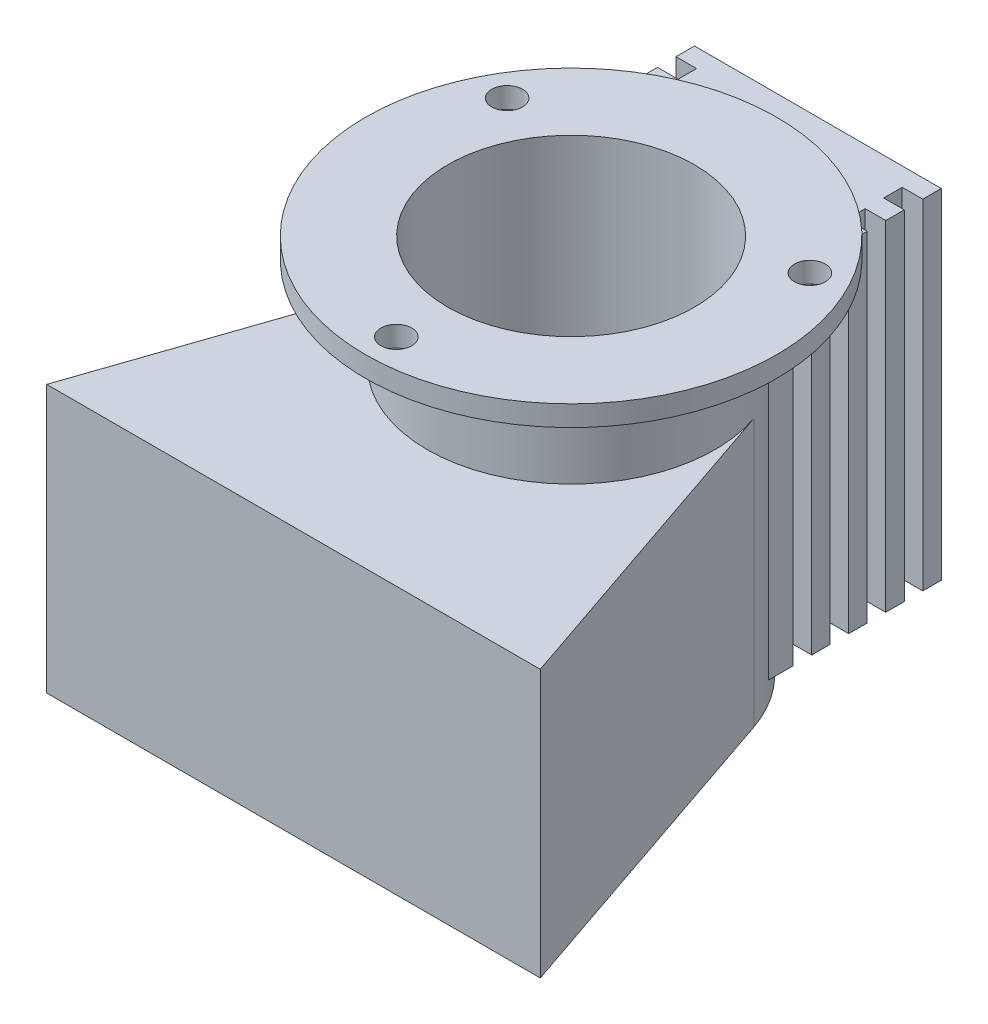
SolidWorks part; units mm, degrees
ref_plane "Front Plane" through (0, 0, 0) normal (0, 0, 1) x (1, 0, 0)
ref_plane "Top Plane" through (0, 0, 0) normal (0, 1, 0) x (1, 0, 0)
ref_plane "Right Plane" through (0, 0, 0) normal (1, 0, 0) x (0, 0, -1)
sketch "Sketch1" plane through (0, 0, 0) normal (0, 1, 0) x (1, 0, 0)
  line L0 (0, 11.2625) -> (0, -11.62) construction
  line L1 (-17.5363, 0) -> (17.5363, 0) construction
  line L2 (-6, -6.75) -> (6, -6.75)
  line L3 (-6, -6.75) -> (-3.3126, 1.1298)
  line L4 (6, -6.75) -> (3.3126, 1.1298)
  circle A0 centre (0, 0) radius 3.5
  point P9 (0, -6.75)
  dimension "D1" = 7
  dimension "D2" = 12
  dimension "D3" = 6.75
extrude "Boss-Extrude2" add sketch "Sketch1" along normal blind 8.75 contours A0 L3 region at (0, 0, 0)
extrude "Boss-Extrude3" add sketch "Sketch1<3>" along normal blind 6.5 contours A0 L3 L2 L4 region at (0, 0, 4.5241)
sketch "Sketch1<3>" plane through (0, 0, 0) normal (0, 1, 0) x (1, 0, 0) same geometry as "Sketch1"
sketch "Sketch2" plane through (0, 8.75, 0) normal (0, 1, 0) x (1, 0, 0)
  circle A0 centre (0, 0) radius 5
  dimension "D1" = 10
extrude "Boss-Extrude4" add sketch "Sketch2" along normal blind 0.5 contours A0
ref_plane "Plane1" through (0, 0, -6) normal (0, 0, 1) x (1, 0, 0)
sketch "Sketch4" plane through (0, 0, -6) normal (0, 0, 1) x (1, 0, 0)
  line L0 (-3.3126, 0) -> (3.3126, 0) construction
  line L1 (3, 0.5) -> (-3, 0.5)
  line L2 (3, 0.5) -> (3, 8.75)
  line L3 (3, 8.75) -> (-3, 8.75)
  line L4 (-3, 0.5) -> (-3, 8.75)
  point P4 (0, 0.5)
  dimension "D1" = 6
  dimension "D2" = 8.25
  dimension "D3" = 0.5
extrude "Boss-Extrude5" add sketch "Sketch4" along normal blind 6
sketch "Sketch5" plane through (0, 8.75, 0) normal (0, 1, 0) x (1, 0, 0)
  line L0 (3, 5.55) -> (3, 5.1)
  line L1 (3, 4) -> (3, 6) construction
  line L2 (3, 5.55) -> (2.5, 5.55)
  line L3 (2.5, 5.55) -> (2.5, 5.1)
  line L4 (2.5, 5.1) -> (3, 5.1)
  line L5 (3, 6) -> (-3, 6) construction
  dimension "D1" = 0.45
  dimension "D2" = 0.45
  dimension "D3" = 0.5
extrude "Cut-Extrude2" cut sketch "Sketch5" against normal through all
pattern_linear "LPattern1" count 4 spacing 0.9 along (0, 0, 1) count 2 spacing 5.5 along (-1, 0, 0) of "Cut-Extrude2"
sketch "Sketch6" plane through (0, 9.25, 0) normal (0, 1, 0) x (1, 0, 0)
  circle A0 centre (0, 0) radius 3
  circle A1 centre (0, 0) radius 0.75
  dimension "D1" = 6
  dimension "D2" = 1.5
extrude "Cut-Extrude3" cut sketch "Sketch6" against normal blind 8.75
sketch "Sketch7" plane through (0, 9.25, 0) normal (0, 1, 0) x (1, 0, 0)
  circle A0 centre (0, 0) radius 0.75
  dimension "D1" = 1.5
extrude "Cut-Extrude4" cut sketch "Sketch7" against normal through all
sketch "Sketch8" plane through (0, 9.25, 0) normal (0, 1, 0) x (1, 0, 0)
  line L0 (0, 7.2372) -> (0, -8.5101) construction
  line L1 (-11.2817, 0) -> (8.3438, 0) construction
  circle A0 centre (0, -4.25) radius 0.375
  circle A1 centre (0, 0) radius 4.25 construction
  circle A2 centre (-3.6806, 2.125) radius 0.375
  circle A3 centre (3.6806, 2.125) radius 0.375
  point P16 (0, 0)
  dimension "D1" = 0.75
  dimension "D2" = 8.5
  dimension "D3" = 3
extrude "Cut-Extrude5" cut sketch "Sketch8" against normal blind 0.5
